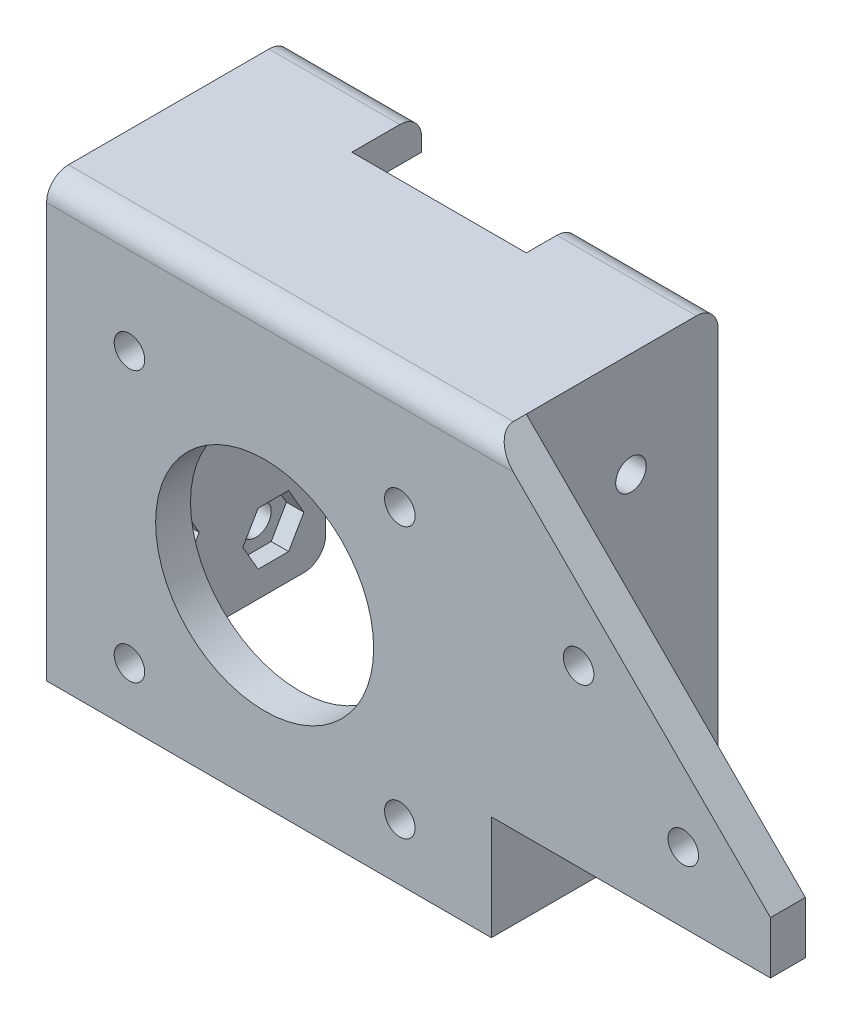
SolidWorks part; units mm, degrees
ref_plane "Front Plane" through (0, 0, 0) normal (0, 0, 1) x (1, 0, 0)
ref_plane "Top Plane" through (0, 0, 0) normal (0, 1, 0) x (1, 0, 0)
ref_plane "Right Plane" through (0, 0, 0) normal (1, 0, 0) x (0, 0, -1)
sketch "Sketch1" plane through (0, 0, 0) normal (0, 0, 1) x (1, 0, 0)
  line L0 (-50.3416, 0) -> (46.1674, 0) construction
  line L1 (0, -28.4394) -> (0, 79.8206) construction
  line L2 (58, 18) -> (26, 50)
  line L4 (-25, 0) -> (-25, 50)
  line L5 (-25, 50) -> (26, 50)
  line L6 (58, 12) -> (58, 18)
  line L7 (26, -2.2452) -> (26, 66.7313) construction
  line L10 (58, 12) -> (26, 12)
  line L11 (26, 12) -> (26, 0)
  line L12 (26, 0) -> (-25, 0)
  dimension "D1" = 50
  dimension "D2" = 38
  dimension "D3" = 6
  dimension "D5" = 26
  dimension "D6" = 45
  dimension "D7" = 51
extrude "Boss-Extrude1" add sketch "Sketch1" along normal blind 4
sketch "Sketch2" plane through (0, 0, 4) normal (0, 0, 1) x (1, 0, 0)
  line L0 (-39.1184, 22) -> (54, 22) construction
  line L1 (0, -8.7046) -> (0, 47.1631) construction
  line L2 (58, 18) -> (26, 50) construction
  line L3 (-15.5, 6.5) -> (15.5, 6.5) construction
  line L4 (-15.5, 6.5) -> (-15.5, 37.5) construction
  line L5 (-15.5, 37.5) -> (15.5, 37.5) construction
  line L6 (15.5, 6.5) -> (15.5, 37.5) construction
  line L7 (-15.5, 6.5) -> (15.5, 37.5) construction
  line L8 (-15.5, 37.5) -> (15.5, 6.5) construction
  line L9 (-25, 0) -> (26, 0) construction
  circle A0 centre (0, 22) radius 12.5
  circle A1 centre (15.5, 6.5) radius 1.75
  circle A2 centre (15.5, 37.5) radius 1.75
  circle A3 centre (-15.5, 37.5) radius 1.75
  circle A4 centre (-15.5, 6.5) radius 1.75
  point P4 (0, 22)
  dimension "D1" = 3.5
  dimension "D4" = 25
  dimension "D2" = 31
  dimension "D3" = 22
extrude "Cut-Extrude1" cut sketch "Sketch2" against normal through all
sketch "Sketch9" plane through (0, 0, 0) normal (0, 0, -1) x (-1, 0, 0)
  line L0 (-61, 20) -> (-36, 20) construction
  line L1 (-36, 20) -> (-36, 48.0747) construction
  line L2 (-26, -5.4794) -> (-26, 53.2688) construction
  line L3 (-26, 12) -> (-58, 12) construction
  circle A1 centre (-48, 20) radius 1.75
  circle A2 centre (-36, 32) radius 1.75
  dimension "D5" = 3.5
  dimension "D1" = 12
  dimension "D3" = 12
  dimension "D4" = 8
  dimension "D2" = 10
extrude "Cut-Extrude2" cut sketch "Sketch9" against normal blind 4
sketch "Sketch13" plane through (0, 0, 4) normal (0, 0, 1) x (1, 0, 0)
  line L8 (-25, 34.0255) -> (-45, 34.0255)
  line L9 (-25, 50) -> (-25, 0) construction
  line L10 (-45, 34.0255) -> (-45, 96.6007)
  line L11 (-45, 96.6007) -> (-32.0913, 96.6007)
  line L13 (58, 18) -> (26, 50) construction
  line L14 (26, 50) -> (20, 56)
  line L15 (-25, 34.0255) -> (-25, 50)
  line L17 (-32.0913, 96.6007) -> (-32.0913, 74.4017)
  line L20 (20, 56) -> (-3.8448, 56)
  line L21 (26, 50) -> (-25, 50)
  arc A3 (-3.8448, 56) -> (-32.0913, 74.4017) centre (-11.974, 74.4017) cw
  dimension "D1" = 20
  dimension "D2" = 6
extrude "Boss-Extrude7" [suppressed] add sketch "Sketch13" against normal blind 4
sketch "Sketch16" [suppressed] plane through (0, 0, 4) normal (0, 0, 1) x (1, 0, 0)
  line L0 (-38.5457, 92.6569) -> (2.0281, 52.0832) construction
  line L1 (-45, 34.0255) -> (-25, 34.0255) construction
  line L2 (-38.5457, 96.6007) -> (-38.5457, 85.5222) construction
  line L3 (-32.0913, 96.6007) -> (-45, 96.6007) construction
  circle A0 centre (2.0281, 52.0832) radius 2
  circle A1 centre (-38.5457, 92.6569) radius 2
  dimension "D3" = 4
  dimension "D1" = 57.38
  dimension "D2" = 45
extrude "Cut-Extrude6" [suppressed] cut sketch "Sketch16" against normal blind 4
sketch "Sketch17" plane through (0, 0, 0) normal (0, 0, -1) x (-1, 0, 0)
  line L0 (-26, 0) -> (-26, 50)
  line L2 (-26, 50) -> (25, 50)
  line L3 (25, 50) -> (25, 0) construction
  line L4 (25, 50) -> (25, 0)
  line L5 (25, 0) -> (21, 0)
  line L6 (25, 0) -> (-26, 0) construction
  line L7 (21, 0) -> (21, 46)
  line L8 (21, 46) -> (-21, 46)
  line L9 (-21, 46) -> (-21, 0)
  line L10 (-21, 0) -> (-26, 0)
  dimension "D1" = 42
  dimension "D2" = 21
  dimension "D3" = 4
extrude "Boss-Extrude8" add sketch "Sketch17" along normal blind 24
sketch "Sketch18" plane through (26, 0, 0) normal (1, 0, 0) x (0, 0, -1)
  line L0 (12, 4.8734) -> (12, 63.3892) construction
  circle A0 centre (12, 38) radius 1.75
  circle A1 centre (12, 20) radius 1.75
  dimension "D1" = 3.5
  dimension "D2" = 20
  dimension "D3" = 18
  dimension "D4" = 12
extrude "Cut-Extrude7" cut sketch "Sketch18" against normal up to surface (5 mm away) up to face at (21, 23, -12)
sketch "Sketch19" plane through (-25, 0, 0) normal (-1, 0, 0) x (0, 0, 1)
  line L0 (-6, 10) -> (-6, 45) construction
  line L2 (4, 0) -> (-24, 0) construction
  line L4 (-18, 6) -> (-6, 6) construction
  line L5 (-18, 6) -> (-18, 41) construction
  line L6 (-18, 41) -> (-6, 41) construction
  line L7 (-6, 6) -> (-6, 41) construction
  circle A0 centre (-18, 6) radius 1.75
  circle A2 centre (-18, 41) radius 1.75
  circle A5 centre (-6, 10) radius 1.75
  circle A6 centre (-6, 45) radius 1.75
  dimension "D5" = 3.5
  dimension "D4" = 12
  dimension "D2" = 6
  dimension "D3" = 35
  dimension "D1" = 6
  dimension "D6" = 35
  dimension "D7" = 10
extrude "Cut-Extrude8" cut sketch "Sketch19" against normal blind 10
sketch "Sketch20" plane through (0, 50, 0) normal (0, 1, 0) x (1, 0, 0)
  line L0 (-25, 24) -> (26, 24) construction
  line L1 (26, 24) -> (-10, 24)
  line L2 (26, 24) -> (26, 22)
  line L4 (-10, 24) -> (-10, 16)
  line L6 (26, 24) -> (26, 0) construction
  line L7 (-10, 16) -> (10, 16)
  line L8 (10, 16) -> (10, 22)
  line L9 (10, 22) -> (26, 22)
  dimension "D1" = 20
  dimension "D2" = 2
  dimension "D3" = 16
  dimension "D4" = 6
extrude "Cut-Extrude9" cut sketch "Sketch20" against normal up to surface (50 mm away) up to face at (0.25, 0, -11)
fillet "Fillet1" radius 2.5 4 edges at (18, 50, -22) (-17.5, 50, -24) (23.5, 0, -22) (-23, 0, -24)
sketch "Sketch22" plane through (-21, 0, 0) normal (1, 0, 0) x (0, 0, -1)
  line L0 (21.5, 0) -> (0, 0) construction
  line L1 (7.5, 42.4019) -> (9, 45)
  line L2 (9, 45) -> (7.5, 47.5981)
  line L3 (7.5, 47.5981) -> (4.5, 47.5981)
  line L4 (4.5, 47.5981) -> (3, 45)
  line L5 (3, 45) -> (4.5, 42.4019)
  line L6 (4.5, 42.4019) -> (7.5, 42.4019)
  circle A0 centre (6, 45) radius 2.5981 construction
  point P0 (6, 45)
  dimension "D1" = 3
extrude "Cut-Extrude11" cut sketch "Sketch22" along normal blind 3 and the other way blind 2
sketch "Sketch23" plane through (-21, 0, 0) normal (1, 0, 0) x (0, 0, -1)
  line L0 (21.5, 0) -> (0, 0) construction
  line L1 (19.75, 37.9689) -> (21.5, 41)
  line L2 (21.5, 41) -> (19.75, 44.0311)
  line L3 (19.75, 44.0311) -> (16.25, 44.0311)
  line L4 (16.25, 44.0311) -> (14.5, 41)
  line L5 (14.5, 41) -> (16.25, 37.9689)
  line L6 (16.25, 37.9689) -> (19.75, 37.9689)
  line L7 (7.75, 6.9689) -> (9.5, 10)
  line L8 (9.5, 10) -> (7.75, 13.0311)
  line L9 (7.75, 13.0311) -> (4.25, 13.0311)
  line L10 (4.25, 13.0311) -> (2.5, 10)
  line L11 (2.5, 10) -> (4.25, 6.9689)
  line L12 (4.25, 6.9689) -> (7.75, 6.9689)
  line L13 (16.25, 2.9689) -> (19.75, 2.9689)
  line L14 (19.75, 2.9689) -> (21.5, 6)
  line L15 (21.5, 6) -> (19.75, 9.0311)
  line L16 (19.75, 9.0311) -> (16.25, 9.0311)
  line L17 (16.25, 9.0311) -> (14.5, 6)
  line L18 (14.5, 6) -> (16.25, 2.9689)
  circle A0 centre (18, 41) radius 3.0311 construction
  circle A1 centre (6, 10) radius 3.0311 construction
  circle A2 centre (18, 6) radius 3.0311 construction
  point P0 (18, 41)
  point P1 (18, 6)
  point P3 (6, 10)
  dimension "D1" = 3.5
extrude "Cut-Extrude12" cut sketch "Sketch23" against normal blind 2
sketch "Sketch24" plane through (21, 0, 0) normal (-1, 0, 0) x (0, 0, 1)
  line L0 (-19.5, 0) -> (0, 0) construction
  line L1 (-10.2403, 41.0479) -> (-13.7597, 41.0479)
  line L2 (-13.7597, 41.0479) -> (-15.5194, 38)
  line L3 (-15.5194, 38) -> (-13.7597, 34.9521)
  line L4 (-13.7597, 34.9521) -> (-10.2403, 34.9521)
  line L5 (-10.2403, 34.9521) -> (-8.4806, 38)
  line L6 (-8.4806, 38) -> (-10.2403, 41.0479)
  line L7 (-10.25, 23.0311) -> (-13.75, 23.0311)
  line L8 (-13.75, 23.0311) -> (-15.5, 20)
  line L9 (-15.5, 20) -> (-13.75, 16.9689)
  line L10 (-13.75, 16.9689) -> (-10.25, 16.9689)
  line L11 (-10.25, 16.9689) -> (-8.5, 20)
  line L12 (-8.5, 20) -> (-10.25, 23.0311)
  circle A0 centre (-12, 38) radius 3.0479 construction
  circle A1 centre (-12, 20) radius 3.0311 construction
  point P0 (-12, 38)
  point P1 (-12, 20)
  dimension "D1" = 3.5
extrude "Cut-Extrude13" cut sketch "Sketch24" against normal blind 2
fillet "Fillet2" radius 2.5 1 edges at (0.5, 50, 4)
equation "\"motor_plate_thickness\"=4"
equation "\"D1@Boss-Extrude1\"=\"motor_plate_thickness\""
equation "\"motor_hub_diameter\"=25"
equation "\"D4@Sketch2\"=\"motor_hub_diameter\""
equation "\"motor_mount_hole_od\"=3.5"
equation "\"D1@Sketch2\"=\"motor_mount_hole_od\""
equation "\"motor_mount_hole_spacing\"=31"
equation "\"D2@Sketch2\"=\"motor_mount_hole_spacing\""
equation "\"D5@Sketch9\"=\"motor_mount_hole_od\""
equation "\"D1@Sketch18\"=\"motor_mount_hole_od\""
equation "\"D5@Sketch19\"=\"motor_mount_hole_od\""
